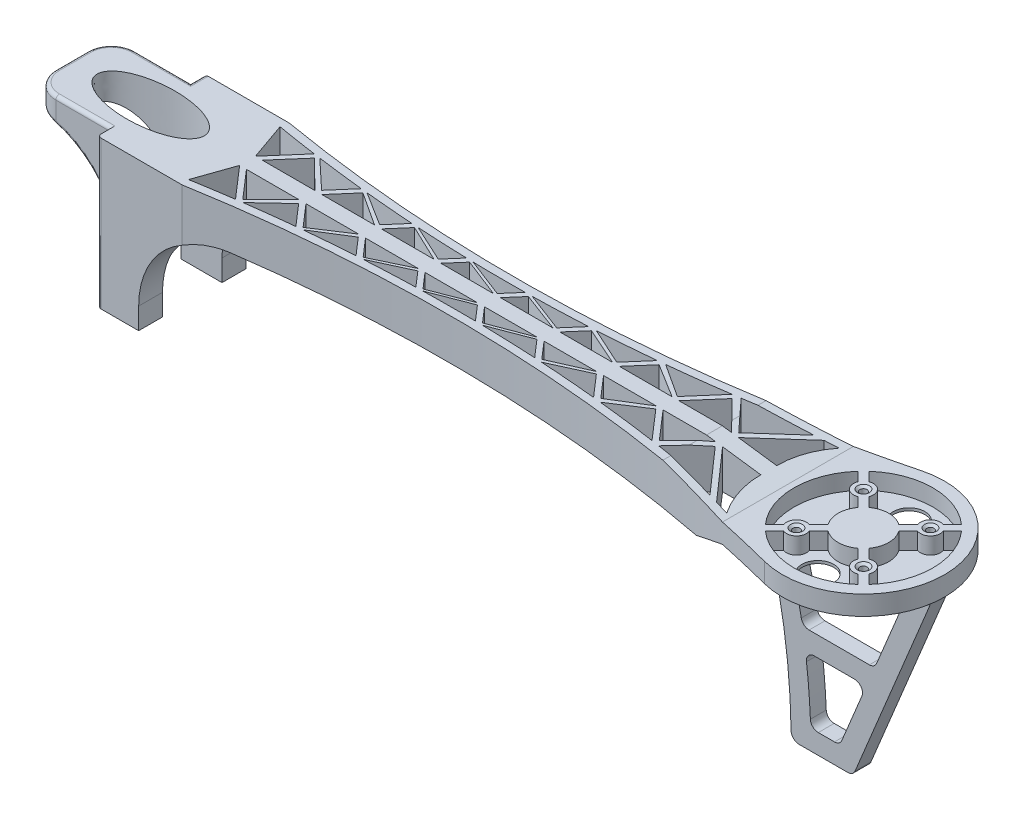
SolidWorks part; units mm, degrees
ref_plane "Front Plane" through (0, 0, 0) normal (0, 0, 1) x (1, 0, 0)
ref_plane "Top Plane" through (0, 0, 0) normal (0, 1, 0) x (1, 0, 0)
ref_plane "Right Plane" through (0, 0, 0) normal (1, 0, 0) x (0, 0, -1)
sketch "Sketch2" plane through (0, 0, 0) normal (0, 0, 1) x (1, 0, 0)
  line L0 (-26.1576, -24.5772) -> (-26.1576, 12.7328)
  line L1 (-26.1576, 12.7328) -> (173.8424, 12.7328)
  line L2 (173.8424, 12.7328) -> (173.8424, 2.3528)
  line L3 (173.8424, 2.3528) -> (5.7724, 2.3528)
  line L4 (-15.7776, -19.1972) -> (-15.7776, -24.5772)
  line L5 (-15.7776, -24.5772) -> (-26.1576, -24.5772)
  arc A0 (5.7724, 2.3528) -> (-15.7776, -19.1972) centre (5.7724, -19.1972) ccw
  dimension "D5" = 21.55
  dimension "D1" = 10.38
  dimension "D2" = 10.38
  dimension "D3" = 200
  dimension "D4" = 37.31
extrude "Boss-Extrude1" add sketch "Sketch2" along normal mid plane 40.89
sketch "Sketch3" plane through (0, 12.7328, 0) normal (0, 1, 0) x (1, 0, 0)
  line L0 (173.8424, 20.445) -> (-26.1576, 20.445) construction
  line L1 (173.8424, -20.445) -> (173.8424, 20.445) construction
  line L2 (173.8424, -20.445) -> (-26.1576, -20.445) construction
  line L3 (-26.1576, 13.5) -> (-4.8376, 13.5)
  line L4 (-26.1576, -20.445) -> (-26.1576, 20.445) construction
  line L5 (-26.1576, 0) -> (-12.3997, 0) construction
  line L6 (-26.1576, -13.5) -> (-4.8376, -13.5)
  circle A0 centre (153.3974, 0) radius 20.445
  arc A1 (-4.8376, 13.5) -> (148.3477, 19.8116) centre (57.0119, 374.4797) ccw
  arc A2 (-4.8376, -13.5) -> (148.3477, -19.8116) centre (57.0119, -374.4797) cw
  line M3 (173.8424, 20.445) -> (-26.1576, 20.445)
  line M4 (-26.1576, 20.445) -> (-26.1576, -20.445)
  line M5 (-26.1576, -20.445) -> (173.8424, -20.445)
  line M6 (173.8424, -20.445) -> (173.8424, 20.445)
  dimension "D1" = 27
  dimension "D2" = 21.32
  dimension "D3" = 366.24
extrude "Cut-Extrude1" cut sketch "Sketch3" against normal blind 40.89 contours L3 A1 A0 M3 M4 | A2 L6 A0 M4 M5 | A0 M5 M6 | A0 M6 M3 region at (55.6922, 12.7328, 15.5019) region at (55.6922, 12.7328, -15.5019) region at (169.2756, 12.7328, -15.8782) region at (169.2756, 12.7328, 15.8782)
sketch "Sketch4" plane through (0, 12.7328, 0) normal (0, 1, 0) x (1, 0, 0)
  line L0 (-1.8376, 0) -> (129.5224, 0) construction
  line L1 (-1.8376, 2) -> (129.5224, 2)
  line L2 (-1.8376, 2) -> (-5.1754, 11.5287)
  line L3 (-1.8376, -2) -> (-5.1754, -11.5287)
  line L4 (-1.8376, -2) -> (129.5224, -2)
  arc A1 (129.5224, 2) -> (133.1207, 14.1908) centre (151.9724, 2) cw
  arc A2 (-5.1754, 11.5287) -> (148.7531, 17.8507) centre (57.0119, 374.4797) ccw
  arc A3 (-5.1754, 11.5287) -> (133.1207, 14.1908) centre (57.0119, 374.4797) ccw
  arc A5 (129.5224, -2) -> (133.1207, -14.1908) centre (151.9724, -2) ccw
  arc A6 (-5.1754, -11.5287) -> (133.1207, -14.1908) centre (57.0119, -374.4797) cw
  dimension "D5" = 22.45
  dimension "D1" = 131.36
  dimension "D2" = 3
  dimension "D3" = 2
  dimension "D4" = 2
extrude "Cut-Extrude3" cut sketch "Sketch4" against normal through all
sketch "Sketch6" plane through (0, 12.7328, 0) normal (0, 1, 0) x (1, 0, 0)
  line L0 (5.0508, 9.9242) -> (-1.8376, 2)
  line L1 (-1.8376, 2) -> (129.5224, 2) construction
  line L2 (-5.1754, 11.5287) -> (-1.8376, 2) construction
  line L3 (-0.1151, 2) -> (6.586, 9.7087)
  line L4 (5.0508, 9.9242) -> (6.586, 9.7087)
  line L5 (-1.8376, 2) -> (-0.1151, 2)
  line L6 (-26.1576, 0) -> (-8.3461, 0) construction
  line L7 (-26.1576, -13.5) -> (-26.1576, 13.5) construction
  line L8 (-1.8376, -2) -> (-0.1151, -2)
  line L9 (5.0508, -9.9242) -> (6.586, -9.7087)
  line L10 (-0.1151, -2) -> (6.586, -9.7087)
  line L11 (5.0508, -9.9242) -> (-1.8376, -2)
  arc A0 (-5.1754, 11.5287) -> (133.1207, 14.1908) centre (57.0119, 374.4797) ccw construction
  dimension "D1" = 49
  dimension "D2" = 1.3
extrude "Boss-Extrude2" add sketch "Sketch6" against normal up to surface (10.3921 mm away) separate body up to face at (-1.6504, -1.2297, -0.0346)
sketch "Sketch7" plane through (0, 12.7328, 0) normal (0, 1, 0) x (1, 0, 0)
  line L3 (-1.8376, 2) -> (129.5224, 2) construction
  line L4 (13.1624, 2) -> (18.5947, 8.2492)
  line L5 (14.8849, 2) -> (20.1761, 8.0868)
  line L6 (28.1624, 2) -> (32.5547, 7.0528)
  line L7 (29.8849, 2) -> (34.186, 6.9479)
  line L8 (43.1624, 2) -> (46.9671, 6.3768)
  line L9 (44.8849, 2) -> (48.653, 6.3346)
  line L10 (58.1624, 2) -> (61.8759, 6.2719)
  line L11 (59.8849, 2) -> (63.622, 6.2991)
  line L12 (73.1624, 2) -> (77.3359, 6.801)
  line L13 (74.8849, 2) -> (79.1494, 6.9058)
  line L14 (88.1624, 2) -> (93.416, 8.0436)
  line L15 (89.8849, 2) -> (95.3061, 8.2363)
  line L16 (103.1624, 2) -> (110.2053, 10.102)
  line L17 (104.8849, 2) -> (112.1837, 10.3963)
  line L18 (118.1624, 2) -> (127.8219, 13.112)
  line L19 (119.8849, 2) -> (129.9046, 13.5264)
  line L20 (-1.8376, 2) -> (-0.1151, 2)
  line L22 (-26.1576, 0) -> (-16.8961, 0) construction
  line L23 (-26.1576, -13.5) -> (-26.1576, 13.5) construction
  line L24 (13.1624, 2) -> (14.8849, 2)
  line L25 (28.1624, 2) -> (29.8849, 2)
  line L26 (43.1624, 2) -> (44.8849, 2)
  line L27 (58.1624, 2) -> (59.8849, 2)
  line L28 (88.1624, 2) -> (89.8849, 2)
  line L29 (73.1624, 2) -> (74.8849, 2)
  line L30 (103.1624, 2) -> (104.8849, 2)
  line L31 (118.1624, 2) -> (119.8849, 2)
  line L32 (118.1624, -2) -> (127.8219, -13.112)
  line L33 (119.8849, -2) -> (129.9046, -13.5264)
  line L34 (118.1624, -2) -> (119.8849, -2)
  line L35 (104.8849, -2) -> (112.1837, -10.3963)
  line L36 (103.1624, -2) -> (110.2053, -10.102)
  line L37 (103.1624, -2) -> (104.8849, -2)
  line L38 (88.1624, -2) -> (89.8849, -2)
  line L39 (88.1624, -2) -> (93.416, -8.0436)
  line L40 (89.8849, -2) -> (95.3061, -8.2363)
  line L41 (73.1624, -2) -> (74.8849, -2)
  line L42 (74.8849, -2) -> (79.1494, -6.9058)
  line L43 (58.1624, -2) -> (59.8849, -2)
  line L44 (58.1624, -2) -> (61.8759, -6.2719)
  line L45 (59.8849, -2) -> (63.622, -6.2991)
  line L46 (73.1624, -2) -> (77.3359, -6.801)
  line L47 (44.8849, -2) -> (48.653, -6.3346)
  line L48 (43.1624, -2) -> (44.8849, -2)
  line L49 (43.1624, -2) -> (46.9671, -6.3768)
  line L50 (28.1624, -2) -> (29.8849, -2)
  line L51 (29.8849, -2) -> (34.186, -6.9479)
  line L52 (28.1624, -2) -> (32.5547, -7.0528)
  line L53 (14.8849, -2) -> (20.1761, -8.0868)
  line L54 (13.1624, -2) -> (18.5947, -8.2492)
  line L55 (13.1624, -2) -> (14.8849, -2)
  arc A2 (18.5947, 8.2492) -> (20.1761, 8.0868) centre (57.0119, 374.4797) ccw
  arc A3 (32.5547, 7.0528) -> (34.186, 6.9479) centre (57.0119, 374.4797) ccw
  arc A4 (46.9671, 6.3768) -> (48.653, 6.3346) centre (57.0119, 374.4797) ccw
  arc A5 (61.8759, 6.2719) -> (63.622, 6.2991) centre (57.0119, 374.4797) ccw
  arc A6 (77.3359, 6.801) -> (79.1494, 6.9058) centre (57.0119, 374.4797) ccw
  arc A7 (93.416, 8.0436) -> (95.3061, 8.2363) centre (57.0119, 374.4797) ccw
  arc A8 (110.2053, 10.102) -> (112.1837, 10.3963) centre (57.0119, 374.4797) ccw
  arc A9 (127.8219, 13.112) -> (129.9046, 13.5264) centre (57.0119, 374.4797) ccw
  arc A10 (127.8219, -13.112) -> (129.9046, -13.5264) centre (57.0119, -374.4797) cw
  arc A11 (110.2053, -10.102) -> (112.1837, -10.3963) centre (57.0119, -374.4797) cw
  arc A12 (93.416, -8.0436) -> (95.3061, -8.2363) centre (57.0119, -374.4797) cw
  arc A13 (77.3359, -6.801) -> (79.1494, -6.9058) centre (57.0119, -374.4797) cw
  arc A14 (61.8759, -6.2719) -> (63.622, -6.2991) centre (57.0119, -374.4797) cw
  arc A15 (46.9671, -6.3768) -> (48.653, -6.3346) centre (57.0119, -374.4797) cw
  arc A16 (32.5547, -7.0528) -> (34.186, -6.9479) centre (57.0119, -374.4797) cw
  arc A17 (18.5947, -8.2492) -> (20.1761, -8.0868) centre (57.0119, -374.4797) cw
  arc M30 (-5.1754, 11.5287) -> (133.1207, 14.1908) centre (57.0119, 374.4797) ccw
  line M32 (129.5224, 2) -> (-1.8376, 2)
  arc M40 (133.1207, -14.1908) -> (-5.1754, -11.5287) centre (57.0119, -374.4797) ccw
  line M42 (-1.8376, -2) -> (129.5224, -2)
  dimension "D2" = 15
  dimension "D3" = 15
extrude "Boss-Extrude3" add sketch "Sketch7" against normal up to surface (10.38 mm away) contours L33 L32 M42 M40 | L40 L39 M42 M40 | L15 L14 M32 M30 | L17 L16 M32 M30 | L13 L12 M32 M30 | L7 L6 M32 M30 | L9 L8 M32 M30 | L49 L47 M42 M40 | L52 L51 M42 M40 | L37 L35 A11 L36 | L18 A9 L19 L31 | L42 A13 L46 L41 | L45 A14 L44 L43 | L11 A5 L10 L27 | L53 A17 L54 L55 | L4 A2 L5 L24 region at (31.1938, 12.7328, -4.5) region at (45.9152, 12.7328, -4.1776) region at (76.136, 12.7328, -4.4264) region at (91.6967, 12.7328, -5.0698) region at (107.6141, 12.7328, -6.1245) region at (123.9487, 12.7328, 7.6596) region at (91.6967, 12.7328, 5.0698) region at (45.9152, 12.7328, 4.1776) region at (31.1938, 12.7328, 4.5) up to face at (73.4515, 2.3528, 0)
sketch "Sketch8" plane through (0, 12.7328, 0) normal (0, 1, 0) x (1, 0, 0)
  line L0 (5.0508, 9.9242) -> (13.1624, 2)
  line L1 (13.1624, 2) -> (14.8849, 2)
  line L2 (14.8849, 2) -> (6.683, 9.6953)
  line L3 (6.683, 9.6953) -> (5.0508, 9.9242)
  line L4 (18.5947, 8.2492) -> (28.1624, 2)
  line L5 (28.1624, 2) -> (29.8849, 2)
  line L6 (29.8849, 2) -> (20.1761, 8.0868)
  line L7 (20.1761, 8.0868) -> (18.5947, 8.2492)
  line L8 (13.1624, -2) -> (14.8849, -2)
  line L9 (6.683, -9.6953) -> (5.0508, -9.9242)
  line L10 (5.0508, -9.9242) -> (13.1624, -2)
  line L11 (14.8849, -2) -> (6.683, -9.6953)
  line L12 (28.1624, -2) -> (29.8849, -2)
  line L13 (18.5947, -8.2492) -> (28.1624, -2)
  line L14 (29.8849, -2) -> (20.1761, -8.0868)
  line L15 (20.1761, -8.0868) -> (18.5947, -8.2492)
  line L16 (-26.1576, 0) -> (-13.5119, 0) construction
  line L17 (-26.1576, -13.5) -> (-26.1576, 13.5) construction
  line L27 (43.1624, 2) -> (46.9671, 6.3768) construction
  line L69 (43.1624, -2) -> (46.9671, -6.3768)
  arc A1 (-5.1754, 11.5287) -> (18.5947, 8.2492) centre (57.0119, 374.4797) ccw construction
extrude "Boss-Extrude4" add sketch "Sketch8" against normal up to surface (10.38 mm away) contours L2 L3 L0 L1 | L4 L5 L6 L7 | L13 L12 L14 L15 | L10 L8 L11 L9 region at (10.0845, 12.7328, -5.7676) up to face at (35.0845, 2.3528, 0)
sketch "Sketch9" plane through (0, 12.7328, 0) normal (0, 1, 0) x (1, 0, 0)
  line L0 (32.5547, 7.0528) -> (43.1624, 2)
  line L1 (43.1624, 2) -> (44.8849, 2)
  line L2 (44.8849, 2) -> (34.186, 6.9479)
  line L3 (34.186, 6.9479) -> (32.5547, 7.0528)
  line L4 (46.9671, 6.3768) -> (58.1624, 2)
  line L5 (58.1624, 2) -> (59.8849, 2)
  line L6 (59.8849, 2) -> (48.653, 6.3346)
  line L7 (48.653, 6.3346) -> (46.9671, 6.3768)
  line L8 (61.8759, 6.2719) -> (73.1624, 2)
  line L9 (73.1624, 2) -> (74.8849, 2)
  line L10 (74.8849, 2) -> (63.622, 6.2991)
  line L11 (63.622, 6.2991) -> (61.8759, 6.2719)
  line L12 (61.8759, 6.2719) -> (61.9604, 6.3487)
  line L13 (77.3359, 6.801) -> (88.1624, 2)
  line L14 (88.1624, 2) -> (89.8849, 2)
  line L15 (89.8849, 2) -> (79.1494, 6.9058)
  line L16 (79.1494, 6.9058) -> (77.3359, 6.801)
  line L17 (93.416, 8.0436) -> (103.1624, 2)
  line L18 (103.1624, 2) -> (104.8849, 2)
  line L19 (104.8849, 2) -> (95.3061, 8.2363)
  line L20 (95.3061, 8.2363) -> (93.416, 8.0436)
  line L21 (93.416, 8.0436) -> (93.3624, 8.0612)
  line L22 (110.2053, 10.102) -> (118.1624, 2)
  line L23 (118.1624, 2) -> (119.8849, 2)
  line L24 (119.8849, 2) -> (112.1837, 10.3963)
  line L25 (112.1837, 10.3963) -> (110.2053, 10.102)
  line L26 (-26.1576, 0) -> (-12.6238, 0) construction
  line L27 (-26.1576, -13.5) -> (-26.1576, 13.5) construction
  line L28 (118.1624, -2) -> (119.8849, -2)
  line L29 (119.8849, -2) -> (112.1837, -10.3963)
  line L30 (112.1837, -10.3963) -> (110.2053, -10.102)
  line L31 (110.2053, -10.102) -> (118.1624, -2)
  line L32 (103.1624, -2) -> (104.8849, -2)
  line L33 (104.8849, -2) -> (95.3061, -8.2363)
  line L34 (95.3061, -8.2363) -> (93.416, -8.0436)
  line L35 (93.416, -8.0436) -> (103.1624, -2)
  line L36 (89.8849, -2) -> (79.1494, -6.9058)
  line L37 (77.3359, -6.801) -> (88.1624, -2)
  line L38 (79.1494, -6.9058) -> (77.3359, -6.801)
  line L39 (73.1624, -2) -> (74.8849, -2)
  line L40 (88.1624, -2) -> (89.8849, -2)
  line L41 (74.8849, -2) -> (63.622, -6.2991)
  line L42 (63.622, -6.2991) -> (61.8759, -6.2719)
  line L43 (61.8759, -6.2719) -> (73.1624, -2)
  line L44 (58.1624, -2) -> (59.8849, -2)
  line L45 (59.8849, -2) -> (48.653, -6.3346)
  line L46 (48.653, -6.3346) -> (46.9671, -6.3768)
  line L47 (46.9671, -6.3768) -> (58.1624, -2)
  line L48 (43.1624, -2) -> (44.8849, -2)
  line L49 (34.186, -6.9479) -> (32.5547, -7.0528)
  line L50 (32.5547, -7.0528) -> (43.1624, -2)
  line L51 (44.8849, -2) -> (34.186, -6.9479)
extrude "Boss-Extrude5" add sketch "Sketch9" against normal up to surface (10.38 mm away) contours L19 L20 L17 L18 | L24 L25 L22 L23 | L2 L3 L0 L1 | L4 L5 L6 L7 | L8 L9 L10 L11 | L15 L16 L13 L14 | L31 L28 L29 L30 | L33 L34 L35 L32 | L37 L40 L36 L38 | L41 L42 L43 L39 | L45 L46 L47 L44 | L50 L48 L51 L49 region at (99.0029, 12.7328, -5.1932) region at (114.9384, 12.7328, -6.3098) up to face at (13.0693, 2.3528, 6.9287)
ref_plane "Plane1" through (0, 0, 0) normal (0, 0, 1) x (1, 0, 0)
sketch "Sketch11" plane through (0, 0, 0) normal (0, 0, 1) x (1, 0, 0)
  line L0 (-26.1576, 12.7328) -> (-46.1576, 12.7328)
  line L1 (-46.1576, 12.7328) -> (-46.1576, 7.3028)
  line L2 (-26.1576, -24.5772) -> (-26.1576, 12.7328) construction
  line L3 (-26.1576, -6.689) -> (-26.1576, 12.7328)
  arc A0 (-46.1576, 7.3028) -> (-26.1576, -6.689) centre (-46.1576, -13.9872) cw
  dimension "D1" = 20
  dimension "D3" = 21.29
  dimension "D2" = 5.43
extrude "Boss-Extrude6" add sketch "Sketch11" along normal mid plane 20
sketch "Sketch12" plane through (-26.1576, 0, 0) normal (-1, 0, 0) x (0, 0, 1)
  line L0 (-7.5, -24.5772) -> (-7.5, -10.6872)
  line L1 (13.5, -24.5772) -> (-13.5, -24.5772) construction
  line L2 (-3.5, -6.6872) -> (3.5, -6.6872)
  line L3 (7.5, -10.6872) -> (7.5, -24.5772)
  line L12 (10, -6.689) -> (-10, -6.689)
  line L13 (-10, -6.689) -> (-10, 12.7328)
  line L14 (-10, 12.7328) -> (-13.5, 12.7328)
  line L15 (-13.5, 12.7328) -> (-13.5, -24.5772)
  line L16 (-13.5, -24.5772) -> (13.5, -24.5772)
  line L17 (13.5, -24.5772) -> (13.5, 12.7328)
  line L18 (13.5, 12.7328) -> (10, 12.7328)
  line L19 (10, 12.7328) -> (10, -6.689)
  line L24 (-7.5, -24.5772) -> (7.5, -24.5772)
  arc A0 (3.5, -6.6872) -> (7.5, -10.6872) centre (3.5, -10.6872) cw
  arc A1 (-7.5, -10.6872) -> (-3.5, -6.6872) centre (-3.5, -10.6872) cw
  point P5 (0, -24.5772)
  point P7 (0, -6.6872)
  point P10 (7.5, -6.6872)
  point P13 (-7.5, -6.6872)
  dimension "D3" = 4
  dimension "D1" = 17.89
  dimension "D2" = 15
  dimension "D4" = 0
extrude "Cut-Extrude4" cut sketch "Sketch12" against normal up to surface (12.1315 mm away) up to face at (0.2786, -0.8121, 0.068)
sketch "Sketch13" plane through (0, 12.7328, 0) normal (0, 1, 0) x (1, 0, 0)
  line L0 (-46.1576, -10) -> (-46.1576, 10) construction
  ellipse E0 centre (-26.2376, 0) end of major axis (-39.7376, 0) minor radius 6.1
  dimension "D1" = 27
  dimension "D2" = 6.42
  dimension "D3" = 12.2
extrude "Cut-Extrude6" cut sketch "Sketch13" against normal through all
ref_plane "Plane2" through (0, 0, 30) normal (0, 0, 1) x (1, 0, 0)
ref_plane "Plane3" through (0, 0, 30) normal (0, 0, 1) x (1, 0, 0)
sketch "Sketch14" plane through (0, 0, 30) normal (0, 0, 1) x (1, 0, 0)
  line L0 (115.8424, 12.7328) -> (134.3571, 10.2328)
  line L1 (148.2548, 12.7328) -> (-4.8376, 12.7328) construction
  line L2 (134.3571, 10.2328) -> (173.8424, 10.2328)
  line L3 (173.8424, 2.3528) -> (173.8424, 12.7328) construction
  line L4 (173.8424, 12.7328) -> (148.2548, 12.7328) construction
  line L5 (126.0571, 2.3528) -> (134.3571, 5.3528)
  line L6 (5.7724, 2.3528) -> (148.2548, 2.3528) construction
  line L7 (134.3571, 5.3528) -> (173.8424, 5.3528)
  line L8 (148.2548, 2.3528) -> (173.8424, 2.3528) construction
  line L9 (115.8424, 12.7328) -> (173.8424, 12.7328)
  line L10 (173.8424, 12.7328) -> (173.8424, 2.3528)
  line L11 (173.8424, 2.3528) -> (126.0571, 2.3528)
  dimension "D1" = 2.5
  dimension "D2" = 7.69
  dimension "D3" = 58
  dimension "D4" = 3
  dimension "D5" = 8.3
extrude "Cut-Extrude7" cut sketch "Sketch14" against normal through all contours L10 L9 L0 L2 | L11 L10 L7 L5 region at (149.1781, 11.5619, 30) region at (151.959, 3.8052, 30)
sketch "Sketch15" plane through (0, 10.2328, 0) normal (0, 1, 0) x (1, 0, 0)
  line L0 (141.023, 12.3744) -> (165.7718, -12.3744) construction
  line L1 (153.3974, 0) -> (160.3148, 0) construction
  line L2 (153.3974, 0) -> (153.3974, 8.634) construction
  line L3 (165.7718, 12.3744) -> (141.023, -12.3744) construction
  line L4 (141.7301, 13.0815) -> (166.4789, -11.6673)
  line L5 (166.4789, 11.6673) -> (141.7301, -13.0815)
  line L6 (140.3159, 11.6673) -> (165.0647, -13.0815)
  line L7 (165.0647, 13.0815) -> (140.3159, -11.6673)
  circle A0 centre (153.3974, 0) radius 17.5
  circle A1 centre (144.9574, 8.44) radius 2.5
  circle A2 centre (161.8374, 8.44) radius 2.5
  circle A3 centre (161.8374, -8.44) radius 2.5
  circle A4 centre (144.9574, -8.44) radius 2.5
  circle A5 centre (153.3974, 0) radius 6.38
  dimension "D1" = 35
  dimension "D5" = 5
  dimension "D7" = 12.76
  dimension "D2" = 45
  dimension "D3" = 1
  dimension "D6" = 8.44
  dimension "D4" = 1
extrude "Cut-Extrude9" cut sketch "Sketch15" against normal blind 4.2 contours A5 L7 A2 A0 L4 A1 | A5 L4 A3 A0 L5 A2 | A5 L5 A4 A0 L6 A3 | A5 L6 A1 A0 L7 A4 region at (153.3974, 10.2328, -11.9822) region at (141.4152, 10.2328, 0) region at (165.3796, 10.2328, 0) region at (153.3974, 10.2328, 11.9822)
sketch "Sketch16" plane through (0, 6.0328, 0) normal (0, 1, 0) x (1, 0, 0)
  line L0 (153.3974, 0) -> (167.1745, 0) construction
  circle A0 centre (153.3974, 11.5) radius 4
  circle A1 centre (153.3974, -11.5) radius 4
  dimension "D1" = 11.5
  dimension "D2" = 8
extrude "Cut-Extrude10" cut sketch "Sketch16" against normal through all
hole_wizard "CSK for #0 Flat Head Machine Screw (100)1" positions "Sketch26" profile "Sketch27" countersink size "#0" standard "ANSI Inch" end condition through all
sketch "Sketch26" plane through (0, 10.2328, 0) normal (0, 1, 0) x (1, 0, 0)
  point P0 (144.9574, 8.44)
  point P3 (161.8374, 8.44)
  point P6 (161.8374, -8.44)
  point P9 (144.9574, -8.44)
sketch "Sketch27" plane through (144.9574, 10.2328, -8.44) normal (1, 0, 0) x (0, 0, 1)
  line L0 (0, 0) -> (0, 34.81)
  line L1 (0, 34.81) -> (0.889, 34.81)
  line L2 (0.889, 34.81) -> (0.889, 0.5222)
  line L3 (0.889, 0.5222) -> (1.5113, 0)
  line L5 (1.5113, 0) -> (0, 0)
  line L6 (-0.889, 0.5222) -> (-1.5113, 0) construction
  line L11 (0, -6.35) -> (0, 107.95) construction
  dimension "Thru Hole Dia." = 1.778
  dimension "Thru Hole Depth" = 34.81
  dimension "Near C'Sink Dia." = 3.0226
  dimension "Near C'Sink Angle" = 100
ref_plane "Plane4" through (0, 0, 0) normal (0, 0, 1) x (1, 0, 0)
ref_plane "Plane5" through (0, 0, 0) normal (0, 0, 1) x (1, 0, 0)
sketch "Sketch28" plane through (0, 0, 0) normal (0, 0, 1) x (1, 0, 0)
  line L0 (172.8424, 5.3528) -> (152.7763, -43.1372)
  line L1 (148.2548, 5.3528) -> (173.8424, 5.3528) construction
  line L2 (152.7763, -43.1372) -> (137.1663, -43.1372)
  line L3 (173.8424, 5.3528) -> (173.8424, 10.2328) construction
  line L4 (167.4312, 5.3528) -> (149.4342, -38.1372)
  line L5 (149.4342, -38.1372) -> (142.0881, -38.1372)
  line L6 (135.3401, -19.4173) -> (162.592, -19.4173) construction
  line L7 (135.3401, -21.9173) -> (135.7065, -21.9173)
  line L8 (140.0027, -16.9173) -> (158.2154, -16.9173)
  line L9 (140.7525, -21.9173) -> (156.1463, -21.9173)
  line L10 (135.3401, -16.9173) -> (162.592, -16.9173) construction
  line L11 (168.2224, 7.2647) -> (149.4342, -38.1372) construction
  line L12 (135.3401, -21.9173) -> (162.592, -21.9173) construction
  line L13 (129.9046, 3.7435) -> (134.3571, 5.3528)
  line L14 (134.3571, 5.3528) -> (134.359, 5.3591)
  line L15 (167.4312, 5.3528) -> (172.8424, 5.3528)
  line L16 (140.7525, -21.9173) -> (135.7065, -21.9173)
  line L17 (135.7065, -21.9173) -> (135.6095, -21.7541)
  line L18 (140.0027, -16.9173) -> (140.7525, -21.9173)
  line L19 (156.1463, -21.9173) -> (161.5575, -21.9173)
  line L20 (134.6703, 5.2561) -> (134.6396, 5.3528)
  line L21 (134.3571, 5.3528) -> (148.2548, 5.3528) construction
  line L22 (134.6396, 5.3528) -> (134.359, 5.3591)
  arc A0 (137.1663, -43.1372) -> (129.9046, 3.7435) centre (-17.7937, -43.1372) ccw
  arc A1 (142.0881, -38.1372) -> (140.7525, -21.9173) centre (-17.7937, -43.1372) ccw
  arc A2 (140.0027, -16.9173) -> (134.6703, 5.2561) centre (-17.7937, -43.1372) ccw
  arc A4 (142.0881, -38.1372) -> (134.6703, 5.2561) centre (-17.7937, -43.1372) ccw construction
  dimension "D1" = 48.49
  dimension "D3" = 154.96
  dimension "D2" = 15.61
  dimension "D4" = 1
  dimension "D6" = 2.5
  dimension "D5" = 5
  dimension "D7" = 2.5
extrude "Boss-Extrude7" add sketch "Sketch28" along normal mid plane 4 contours L18 A2 L20 L22 L14 L13 A0 L16 | L8 L18 L9 L4 | L4 L19 L0 L15 | L5 A1 L16 A0 L2 L0 L19 L4 region at (164.4943, -8.2823, 0) region at (156.8578, -32.3994, 0) region at (148.7884, -19.3474, 0) region at (135.6496, -8.567, 0)
fillet "Fillet1" radius 6 2 edges at (-46.1576, 10.0178, 10) (-46.1576, 10.0178, -10)
fillet "Fillet3" radius 0.9 13 edges at (-31.5942, 1.5425, 10) (-43.8391, 7.1762, 8.7378) (-31.5942, 1.5425, -10) (-44.8447, 7.2623, -7.7458) (-33.1576, 12.7328, -10) (-44.4002, 12.7328, -8.2426) (-44.4002, 12.7328, 8.2426) (-46.1576, 12.7328, 0) (-46.1576, 7.3028, 0) (-26.1576, -5.9222, -13.5) (-26.1576, 12.7328, -11.75) (-33.1576, 12.7328, 10) (-26.1576, -5.9222, 13.5)
fillet "Fillet4" radius 2 10 edges at (156.1463, -21.9173, 0) (132.1309, 4.5481, -2) (170.1368, 5.3528, -2) (170.1368, 5.3528, 2) (132.1309, 4.5481, 2) (140.7525, -21.9173, 0) (142.0881, -38.1372, 0) (140.0027, -16.9173, 0) (158.2154, -16.9173, 0) (149.4342, -38.1372, 0)
fillet "Fillet5" radius 2 2 edges at (137.1663, -43.1372, 0) (152.7763, -43.1372, 0)
